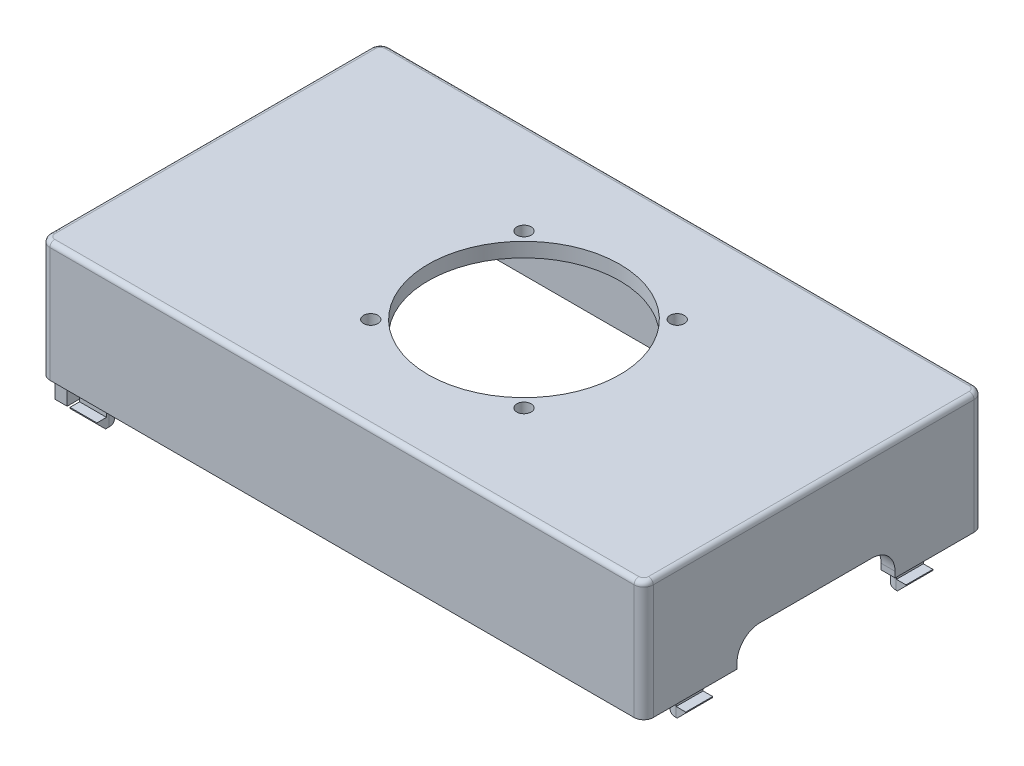
SolidWorks part; units mm, degrees
material "ABS"
ref_plane "Front Plane" through (0, 0, 0) normal (0, 0, 1) x (1, 0, 0)
ref_plane "Top Plane" through (0, 0, 0) normal (0, 1, 0) x (1, 0, 0)
ref_plane "Right Plane" through (0, 0, 0) normal (1, 0, 0) x (0, 0, -1)
sketch "Sketch1" plane through (0, 0, 0) normal (0, 1, 0) x (1, 0, 0)
  line L1 (-63, -35.5) -> (63, -35.5)
  line L2 (-63, -35.5) -> (-63, 35.5)
  line L3 (-63, 35.5) -> (63, 35.5)
  line L4 (63, -35.5) -> (63, 35.5)
  line L5 (-63, -35.5) -> (63, 35.5) construction
  line L6 (-63, 35.5) -> (63, -35.5) construction
  point P0 (0, 0)
  dimension "D1" = 126
  dimension "D2" = 71
extrude "Boss-Extrude1" add sketch "Sketch1" along normal blind 25
sketch "Sketch2" plane through (0, 0, 0) normal (0, -1, 0) x (1, 0, 0)
  line L0 (63, 35.5) -> (63, -35.5) construction
  line L1 (-60.5, 33) -> (60.1, 33)
  line L2 (-60.5, 33) -> (-60.5, -33)
  line L3 (-60.5, -33) -> (60.1, -33)
  line L4 (60.1, 33) -> (60.1, -33)
  line L5 (-63, 35.5) -> (63, 35.5) construction
  line L6 (63, -35.5) -> (-63, -35.5) construction
  line L7 (-63, -35.5) -> (-63, 35.5) construction
  dimension "D1" = 2.9
  dimension "D2" = 2.5
  dimension "D3" = 2.5
  dimension "D4" = 2.5
extrude "Cut-Extrude1" cut sketch "Sketch2" against normal blind 22
sketch "Sketch3" plane through (63, 0, 0) normal (1, 0, 0) x (0, 0, -1)
  line L0 (-35.5, 0) -> (35.5, 0) construction
  line L1 (-16, 0) -> (17, 0)
  line L2 (-16, 0) -> (-16, 6)
  line L3 (-16, 6) -> (17, 6)
  line L4 (17, 0) -> (17, 6)
  line L5 (-35.5, 25) -> (-35.5, 0) construction
  dimension "D1" = 33
  dimension "D2" = 6
  dimension "D3" = 19.5
extrude "Cut-Extrude2" cut sketch "Sketch3" against normal up to next
fillet "Fillet1" radius 4.8 2 edges at (61.55, 6, -17) (61.55, 6, 16)
sketch "Sketch4" plane through (-63, 0, 0) normal (-1, 0, 0) x (0, 0, 1)
  line L0 (-35.5, 25) -> (-35.5, 0) construction
  line L1 (-35.5, 0) -> (35.5, 0) construction
  line L2 (-32.6, 0) -> (-32.6, -19)
  line L3 (-32.6, -19) -> (5, -19)
  line L4 (5, -19) -> (5, -6)
  line L5 (5, -6) -> (32.4, -6)
  line L6 (32.4, -6) -> (32.4, 0)
  line L7 (33, 0) -> (-33, 0) construction
  line L8 (32.4, 0) -> (-32.6, 0)
  line L9 (35.5, 25) -> (35.5, 0) construction
  dimension "D1" = 19
  dimension "D2" = 37.6
  dimension "D3" = 13
  dimension "D4" = 2.9
  dimension "D5" = 3.1
extrude "Boss-Extrude2" add sketch "Sketch4" against normal up to surface (2.5 mm away) up to face at (-60.5, 11, 0)
sketch "Sketch5" plane through (0, 25, 0) normal (0, 1, 0) x (1, 0, 0)
  line L0 (-63, -35.5) -> (63, -35.5) construction
  circle A1 centre (2.5, 0) radius 20
  dimension "D1" = 40
  dimension "D2" = 35.5
  dimension "D3" = 60.5
extrude "Cut-Extrude3" cut sketch "Sketch5" against normal through all
sketch "Sketch6" plane through (0, 25, 0) normal (0, 1, 0) x (1, 0, 0)
  line L0 (-13.5, 16) -> (18.5, 16) construction
  line L1 (18.5, 16) -> (18.5, -16) construction
  line L2 (2.5, 0) -> (2.5, -8.916) construction
  line L3 (-13.5, 16) -> (18.5, -16) construction
  circle A0 centre (-13.5, 16) radius 1.5
  circle A1 centre (18.5, 16) radius 1.5
  circle A2 centre (18.5, -16) radius 1.5
  circle A3 centre (-13.5, -16) radius 1.5
  dimension "D1" = 3
  dimension "D2" = 32
extrude "Cut-Extrude4" cut sketch "Sketch6" against normal through all
fillet "Fillet2" radius 2 4 edges at (-63, 12.5, 35.5) (-63, 12.5, -35.5) (63, 12.5, -35.5) (63, 12.5, 35.5)
fillet "Fillet3" radius 1 8 edges at (-62.4142, 25, 34.9142) (-63, 25, 0) (-62.4142, 25, -34.9142) (0, 25, -35.5) (62.4142, 25, -34.9142) (63, 25, 0) (62.4142, 25, 34.9142) (0, 25, 35.5)
sketch "Sketch7" plane through (0, 0, 0) normal (0, -1, 0) x (1, 0, 0)
  line L0 (63, 33.5) -> (63, 16) construction
  line L1 (-61, 35.5) -> (61, 35.5) construction
  line L2 (61, -35.5) -> (-61, -35.5) construction
  line L3 (57.1993, 23) -> (57.1993, -23) construction
  line L4 (0, 0) -> (57.1993, 0) construction
  line L5 (-63, 5) -> (-63, 32.4) construction
  line L6 (-57.3138, 32.513) -> (-57.3138, 33)
  line L8 (-57.3138, 33) -> (-51.6862, 33)
  line L11 (-51.6862, 32.513) -> (-51.6862, 33)
  line L12 (60.1, 33) -> (-60.5, 33) construction
  line L13 (-57.3138, -32.513) -> (-57.3138, -33)
  line L14 (-57.3138, -33) -> (-51.6862, -33)
  line L16 (-51.6862, -32.513) -> (-51.6862, -33)
  line L17 (-60.5, -33) -> (60.1, -33) construction
  line L18 (60.013, -25.8138) -> (60.1, -25.8138)
  line L19 (60.013, -20.1862) -> (60.1, -20.1862)
  line L20 (60.1, -20.1862) -> (60.1, -25.8138)
  line L22 (60.1, -33) -> (60.1, -17) construction
  line L23 (60.013, 25.8138) -> (60.1, 25.8138)
  line L24 (60.1, 25.8138) -> (60.1, 20.1862)
  line L26 (60.013, 20.1862) -> (60.1, 20.1862)
  line L27 (60.1, 16) -> (60.1, 33) construction
  arc A0 (-57.3138, 32.513) -> (-51.6862, 32.513) centre (-54.5, 32.513) ccw
  arc A1 (-51.6862, -32.513) -> (-57.3138, -32.513) centre (-54.5, -32.513) ccw
  arc A2 (60.013, 25.8138) -> (60.013, 20.1862) centre (60.013, 23) ccw
  arc A3 (60.013, -20.1862) -> (60.013, -25.8138) centre (60.013, -23) ccw
  dimension "D1" = 5.6275
  dimension "D3" = 2.987
  dimension "D4" = 2.987
  dimension "D5" = 46
  dimension "D6" = 8.5
  dimension "D2" = 2.987
extrude "Boss-Extrude3" add sketch "Sketch7" against normal blind 4.7
sketch "Sketch8" plane through (0, 0, 0) normal (0, -1, 0) x (1, 0, 0)
  line L0 (-57.3138, 33) -> (-57.3138, 32.513) construction
  line L1 (-57.3138, -32.513) -> (-57.3138, -33) construction
  line L2 (60.013, 20.1862) -> (60.1, 20.1862) construction
  line L3 (60.013, -25.8138) -> (60.1, -25.8138) construction
  line L4 (-51.6862, 32.513) -> (-51.6862, 33) construction
  line L5 (-57.3138, 33) -> (-57.3138, 32.513)
  line L6 (-51.6862, 32.513) -> (-51.6862, 33)
  line L7 (-57.3138, 33) -> (-51.6862, 33)
  line L8 (-51.6862, -33) -> (-51.6862, -32.513) construction
  line L9 (-57.3138, -32.513) -> (-57.3138, -33)
  line L10 (-51.6862, -33) -> (-51.6862, -32.513)
  line L11 (-57.3138, -33) -> (-51.6862, -33)
  line L12 (60.1, -20.1862) -> (60.013, -20.1862) construction
  line L13 (60.013, -25.8138) -> (60.1, -25.8138)
  line L14 (60.1, -20.1862) -> (60.013, -20.1862)
  line L15 (60.1, -20.1862) -> (60.1, -25.8138)
  line L16 (60.1, 25.8138) -> (60.013, 25.8138) construction
  line L17 (60.013, 20.1862) -> (60.1, 20.1862)
  line L18 (60.1, 25.8138) -> (60.013, 25.8138)
  line L19 (60.1, 25.8138) -> (60.1, 20.1862)
  arc A0 (-57.3138, 32.513) -> (-51.6862, 32.513) centre (-54.5, 32.513) ccw construction
  arc A1 (-57.3138, 32.513) -> (-51.6862, 32.513) centre (-54.5, 32.513) ccw
  arc A2 (-51.6862, -32.513) -> (-57.3138, -32.513) centre (-54.5, -32.513) ccw construction
  arc A3 (-51.6862, -32.513) -> (-57.3138, -32.513) centre (-54.5, -32.513) ccw
  arc A4 (60.013, -20.1862) -> (60.013, -25.8138) centre (60.013, -23) ccw construction
  arc A5 (60.013, 25.8138) -> (60.013, 20.1862) centre (60.013, 23) ccw construction
  arc A6 (60.013, -20.1862) -> (60.013, -25.8138) centre (60.013, -23) ccw
  arc A7 (60.013, 25.8138) -> (60.013, 20.1862) centre (60.013, 23) ccw
extrude "Boss-Extrude4" add sketch "Sketch8" along normal blind 5.3
sketch "Sketch9" plane through (0, 0, 0) normal (1, 0, 0) x (0, 0, -1)
  line L0 (-33, 4.7) -> (-29.6993, 1.3993)
  line L1 (-29.6993, -5.3) -> (-29.6993, 4.7) construction
  line L2 (-29.6993, 1.3993) -> (-29.6993, 4.7)
  line L3 (-29.6993, 4.7) -> (-33, 4.7)
  line L4 (33, 4.7) -> (29.6993, 1.3993)
  line L5 (29.6993, 4.7) -> (29.6993, -5.3) construction
  line L6 (29.6993, 1.3993) -> (29.6993, 4.7)
  line L7 (29.6993, 4.7) -> (33, 4.7)
  dimension "D1" = 45
extrude "Cut-Extrude5" cut sketch "Sketch9" against normal up to surface (60.5 mm away) up to face at (-60.5, -1.25, 1.01)
sketch "Sketch10" plane through (0, 0, -33) normal (0, 0, 1) x (1, 0, 0)
  line L0 (60.1, 4.7) -> (57.1993, 1.7993)
  line L1 (57.1993, 4.7) -> (57.1993, -5.3) construction
  line L2 (57.1993, 1.7993) -> (57.1993, 4.7)
  line L3 (57.1993, 4.7) -> (60.1, 4.7)
extrude "Cut-Extrude6" cut sketch "Sketch10" along normal up to surface (66 mm away) up to face at (-27.35, 6.675, 33)
sketch "Sketch11" plane through (0, 0, 25.8138) normal (0, 0, 1) x (1, 0, 0)
  line L0 (60.1, -3.3) -> (62.1, -3.3)
  line L1 (60.1, -5.3) -> (60.1, 0) construction
  line L2 (62.1, -3.3) -> (62.1, -3.5)
  line L3 (62.1, -3.5) -> (60.3, -5.3)
  line L4 (60.3, -5.3) -> (60.1, -5.3)
  line L5 (60.1, -5.3) -> (60.1, -3.3)
  line L6 (61, 0) -> (63, 0) construction
  dimension "D1" = 2
  dimension "D2" = 0.2
  dimension "D3" = 3.3
  dimension "D4" = 0.2
extrude "Boss-Extrude5" add sketch "Sketch11" against normal up to surface (5.6275 mm away) up to face at (60.0652, -0.2574, 20.1862)
sketch "Sketch12" plane through (0, 0, -20.1862) normal (0, 0, 1) x (1, 0, 0)
  line L0 (60.1, -3.3) -> (62.1, -3.3)
  line L1 (62.1, -3.3) -> (62.1, -3.5)
  line L2 (62.1, -3.5) -> (60.3, -5.3)
  line L3 (60.3, -5.3) -> (60.1, -5.3)
  line L5 (60.1, -3.3) -> (60.1, -5.3)
extrude "Boss-Extrude6" add sketch "Sketch12" against normal up to surface (5.6275 mm away) up to face at (60.0652, -0.2574, -25.8138)
sketch "Sketch13" plane through (-51.6862, 0, 0) normal (1, 0, 0) x (0, 0, -1)
  line L0 (-33, -3.3) -> (-35, -3.3)
  line L1 (-33, -5.3) -> (-33, 0) construction
  line L2 (-35, -3.3) -> (-35, -3.5)
  line L3 (-35, -3.5) -> (-33.2, -5.3)
  line L4 (-33.2, -5.3) -> (-33, -5.3)
  line L5 (-33, -5.3) -> (-33, -3.3)
  line L6 (-35.5, 0) -> (-33.5, 0) construction
  line L7 (33, -5.3) -> (33.2, -5.3)
  line L8 (33.2, -5.3) -> (35, -3.5)
  line L9 (35, -3.5) -> (35, -3.3)
  line L10 (35, -3.3) -> (33, -3.3)
  line L11 (33, -5.3) -> (33, 0) construction
  line L12 (33, -3.3) -> (33, -5.3)
  dimension "D1" = 0.2
  dimension "D2" = 0.2
  dimension "D3" = 3.3
  dimension "D4" = 2
extrude "Boss-Extrude7" add sketch "Sketch13" against normal up to surface (5.6275 mm away) up to face at (-57.3138, -0.3374, -32.8052)
fillet "Fillet4" radius 5 2 edges at (-61.75, -19, -32.6) (-61.75, -19, 5)
